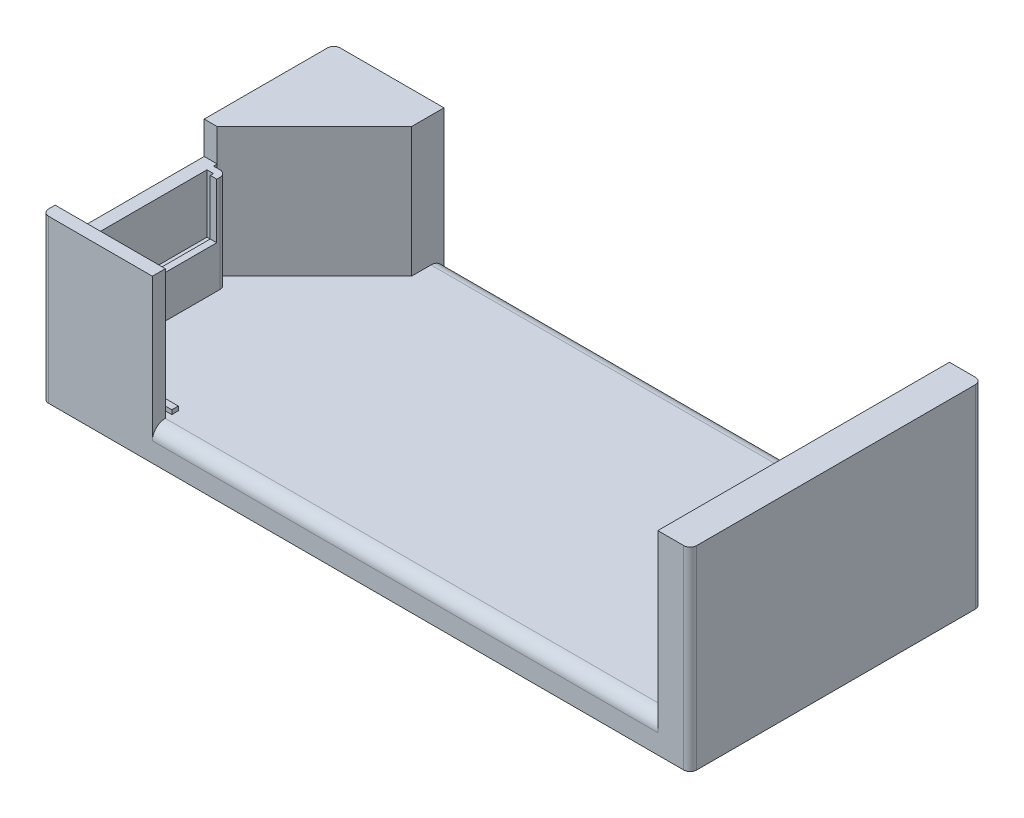
SolidWorks part; units mm, degrees
ref_plane "Front Plane" through (0, 0, 0) normal (0, 0, 1) x (1, 0, 0)
ref_plane "Top Plane" through (0, 0, 0) normal (0, 1, 0) x (1, 0, 0)
ref_plane "Right Plane" through (0, 0, 0) normal (1, 0, 0) x (0, 0, -1)
sketch "Sketch1" plane through (0, 0, 0) normal (0, 1, 0) x (1, 0, 0)
  line L0 (-48, -22.5) -> (-48, 2.5)
  line L1 (-50, -22.5) -> (50, -22.5)
  line L2 (-50, -22.5) -> (-50, 22.5)
  line L3 (-50, 22.5) -> (50, 22.5)
  line L4 (50, -22.5) -> (50, 22.5)
  line L5 (-50, -22.5) -> (50, 22.5) construction
  line L6 (-50, 22.5) -> (50, -22.5) construction
  line L7 (50, -22.5) -> (45, -22.5)
  line L8 (50, -22.5) -> (50, 22.5)
  line L9 (50, 22.5) -> (45, 22.5)
  line L10 (45, -22.5) -> (45, 22.5)
  line L11 (50, -22.5) -> (45, 22.5) construction
  line L12 (50, 22.5) -> (45, -22.5) construction
  line L13 (-48, 2.5) -> (-28, 22.5)
  line L14 (-48, -20.5) -> (-33, -20.5)
  line L15 (-33, -20.5) -> (-33, -22.5)
  line L16 (-33, 17.5) -> (-33, 22.5)
  line L17 (-48, -20.5) -> (-50, -20.5)
  line L18 (-48, 2.5) -> (-50, 2.5)
  line L20 (-48, -19.5) -> (-33, -19.5)
  line L21 (-48, -19.5) -> (-48, -18.5)
  line L22 (-48, -18.5) -> (-33, -18.5)
  line L23 (-33, -19.5) -> (-33, -18.5)
  line L24 (-48, -19.5) -> (-33, -18.5) construction
  line L25 (-48, -18.5) -> (-33, -19.5) construction
  point P0 (0, 0)
  point P8 (47.5, 0)
  point P23 (-40.5, -19)
  dimension "D1" = 100
  dimension "D2" = 45
  dimension "D3" = 5
  dimension "D4" = 135
  dimension "D5" = 2
  dimension "D6" = 15
  dimension "10" = 20
  dimension "D7" = 15
  dimension "D8" = 2
  dimension "D9" = 1
  dimension "D10" = 1
extrude "Boss-Extrude1" add sketch "Sketch1" against normal blind 5 contours L18 L13 L16 L3 L2 | L14 L15 L1 L10 L3 L13 L0 | L16 L13 L3 | L10 L1 L4 L3 | L0 L18 L2 L17 | L15 L14 L0 L1 | L0 L17 L2 L1 | L20 L23 L22 L0 region at (-49, 0, 21.5) region at (-40.5, 0, 21.5) region at (-49, 0, 9) region at (0.9674, 0, 0.5677) region at (-40.5, 0, 19) region at (47.5, 0, 0) region at (-43.2308, 0, -14.9725) region at (-31.3333, 0, -20.8333)
extrude "Boss-Extrude2" add sketch "Sketch1<4>" along normal blind 25 contours L10 L1 L4 L3 region at (47.5, 0, 0)
sketch "Sketch1<4>" plane through (0, 0, 0) normal (0, 1, 0) x (1, 0, 0) same geometry as "Sketch1"
extrude "Boss-Extrude3" add sketch "Sketch1<5>" along normal blind 20 contours L15 L14 L0 L1 | L0 L17 L2 L1 region at (-49, 0, 21.5) region at (-40.5, 0, 21.5)
sketch "Sketch1<5>" plane through (0, 0, 0) normal (0, 1, 0) x (1, 0, 0) same geometry as "Sketch1"
extrude "Boss-Extrude4" add sketch "Sketch1<6>" along normal blind 20 contours L18 L13 L16 L3 L2 region at (-43.2308, 0, -14.9725)
sketch "Sketch1<6>" plane through (0, 0, 0) normal (0, 1, 0) x (1, 0, 0) same geometry as "Sketch1"
extrude "Boss-Extrude5" add sketch "Sketch1<8>" along normal blind 15 contours L0 L18 L2 L17 region at (-49, 0, 9)
sketch "Sketch1<8>" plane through (0, 0, 0) normal (0, 1, 0) x (1, 0, 0) same geometry as "Sketch1"
extrude "Boss-Extrude6" add sketch "Sketch1<9>" along normal blind 0.65 from surface contours L20 L23 L22 L0 region at (-40.5, 0, 19) starting at face at (-17.25, 0, 2.625)
sketch "Sketch1<9>" plane through (0, 0, 0) normal (0, 1, 0) x (1, 0, 0) same geometry as "Sketch1"
sketch "Sketch4" plane through (0, 0, 20.5) normal (0, 0, -1) x (-1, 0, 0)
  line L0 (33, 20) -> (33, 0) construction
  line L1 (42, 0) -> (43.5, 0)
  line L2 (42, 0) -> (42, 15)
  line L3 (42, 15) -> (43.5, 15)
  line L4 (43.5, 0) -> (43.5, 15)
  line L5 (42, 0) -> (43.5, 15) construction
  line L6 (42, 15) -> (43.5, 0) construction
  line L7 (50, 0) -> (-50, 0) construction
  line L9 (42, 15) -> (41.5, 15)
  line L10 (42, 15) -> (42, 0)
  line L11 (42, 0) -> (41.5, 0)
  line L12 (41.5, 15) -> (41.5, 0)
  line L13 (42, 15) -> (41.5, 0) construction
  line L14 (42, 0) -> (41.5, 15) construction
  point P4 (42.75, 7.5)
  point P9 (42.75, 15)
  point P12 (41.75, 7.5)
  line M5 (33, 0) -> (48, 0)
  dimension "D1" = 9
  dimension "D2" = 1.5
  dimension "D3" = 15
  dimension "D4" = 0.5
extrude "Boss-Extrude7" add sketch "Sketch4" along normal blind 1 contours L4 L3 L2 M5 region at (-42.75, 7.5, 20.5)
extrude "Boss-Extrude8" add sketch "Sketch4<4>" along normal blind 1 from surface contours L9 L12 L2 M5 | L4 L3 L2 M5 region at (-42.75, 7.5, 20.5) region at (-41.75, 7.5, 20.5) starting at face at (-42.75, 7.825, 19.5)
sketch "Sketch4<4>" plane through (0, 0, 20.5) normal (0, 0, -1) x (-1, 0, 0) same geometry as "Sketch4"
sketch "Sketch5" plane through (-48, 0, 0) normal (1, 0, 0) x (0, 0, -1)
  line L0 (-20.5, 15) -> (2.5, 15) construction
  line L1 (-17.0662, 15) -> (0.9338, 15)
  line L2 (-17.0662, 15) -> (-17.0662, 6)
  line L3 (-17.0662, 6) -> (0.9338, 6)
  line L4 (0.9338, 15) -> (0.9338, 6)
  line L5 (-17.0662, 15) -> (0.9338, 6) construction
  line L6 (-17.0662, 6) -> (0.9338, 15) construction
  line L7 (-18.5, 0) -> (2.5, 0) construction
  line L8 (-17.0662, 15) -> (-18.0662, 15)
  line L9 (-17.0662, 15) -> (-17.0662, 6)
  line L10 (-17.0662, 6) -> (-18.0662, 6)
  line L11 (-18.0662, 15) -> (-18.0662, 6)
  line L12 (-17.0662, 15) -> (-18.0662, 6) construction
  line L13 (-17.0662, 6) -> (-18.0662, 15) construction
  line L14 (-18.0662, 6) -> (1.9338, 6)
  line L15 (-18.0662, 6) -> (-18.0662, 0)
  line L16 (-18.0662, 0) -> (1.9338, 0)
  line L17 (1.9338, 6) -> (1.9338, 0)
  line L18 (-18.0662, 6) -> (1.9338, 0) construction
  line L19 (-18.0662, 0) -> (1.9338, 6) construction
  line L20 (1.9338, 6) -> (0.9338, 6)
  line L21 (1.9338, 6) -> (1.9338, 15)
  line L22 (1.9338, 15) -> (0.9338, 15)
  line L23 (0.9338, 6) -> (0.9338, 15)
  line L24 (1.9338, 6) -> (0.9338, 15) construction
  line L25 (1.9338, 15) -> (0.9338, 6) construction
  line L27 (-17.0662, 6) -> (-16.5662, 6)
  line L28 (-17.0662, 6) -> (-17.0662, 15)
  line L29 (-17.0662, 15) -> (-16.5662, 15)
  line L30 (-16.5662, 6) -> (-16.5662, 15)
  line L31 (-17.0662, 6) -> (-16.5662, 15) construction
  line L32 (-17.0662, 15) -> (-16.5662, 6) construction
  line L33 (0.4338, 6) -> (0.9338, 6)
  line L34 (0.4338, 6) -> (0.4338, 15)
  line L35 (0.4338, 15) -> (0.9338, 15)
  line L36 (0.9338, 6) -> (0.9338, 15)
  line L37 (0.4338, 6) -> (0.9338, 15) construction
  line L38 (0.4338, 15) -> (0.9338, 6) construction
  line L39 (-18.0662, 6) -> (0.9338, 6)
  line L40 (-18.0662, 6) -> (-18.0662, 6.5)
  line L41 (-18.0662, 6.5) -> (0.9338, 6.5)
  line L42 (0.9338, 6) -> (0.9338, 6.5)
  line L43 (-18.0662, 6) -> (0.9338, 6.5) construction
  line L44 (-18.0662, 6.5) -> (0.9338, 6) construction
  point P4 (-8.0662, 10.5)
  point P11 (-17.5662, 10.5)
  point P13 (-8.0662, 3)
  point P16 (1.4338, 10.5)
  point P20 (-16.8162, 10.5)
  point P24 (0.6838, 10.5)
  point P26 (-8.5662, 6.25)
  line M7 (-18.5, 0) -> (2.5, 0)
  line M9 (2.5, 15) -> (-20.5, 15)
  dimension "D1" = 9
  dimension "D2" = 18
  dimension "D3" = 1
  dimension "D4" = 1
  dimension "D5" = 0.5
  dimension "D6" = 0.5
  dimension "D7" = 0.5
extrude "Boss-Extrude9" add sketch "Sketch5" along normal blind 1 contours L17 L14 L3 L10 L15 M7 | L11 L41 L2 M9 | L41 L11 L10 L28 | L14 L21 L4 L36 M9 region at (-48, 10.75, 17.5662) region at (-48, 6.25, 17.5662) region at (-48, 3, 8.0662) region at (-48, 10.5, -1.4338)
extrude "Boss-Extrude11" add sketch "Sketch5<5>" along normal blind 1 from surface contours L11 L41 L2 M9 | L2 L41 L30 L1 | L41 L11 L10 L28 | L41 L28 L3 L30 | L17 L14 L3 L10 L15 M7 | L41 L30 L14 L34 | L34 L41 L4 M9 | L41 L34 L3 L36 | L14 L21 L4 L36 M9 region at (-48, 10.75, 16.8162) region at (-48, 10.75, 17.5662) region at (-48, 6.25, 16.8162) region at (-48, 6.25, 17.5662) region at (-48, 10.75, -0.6838) region at (-48, 6.25, 8.0662) region at (-48, 3, 8.0662) region at (-48, 10.5, -1.4338) region at (-48, 6.25, -0.6838) starting at face at (-47, 9, 8.0662)
sketch "Sketch5<5>" plane through (-48, 0, 0) normal (1, 0, 0) x (0, 0, -1) same geometry as "Sketch5"
fillet "Fillet1" radius 1 3 edges at (-46, 7.5, -1.9338) (-43.5, 7.825, 18.5) (-46, 7.5, 18.0662)
fillet "Fillet2" radius 1 4 edges at (50, 10, 22.5) (-50, 7.5, 22.5) (50, 10, -22.5) (-50, 7.5, -22.5)
fillet "Fillet3" radius 2 2 edges at (6, 0, 22.5) (6, 0, -22.5)
